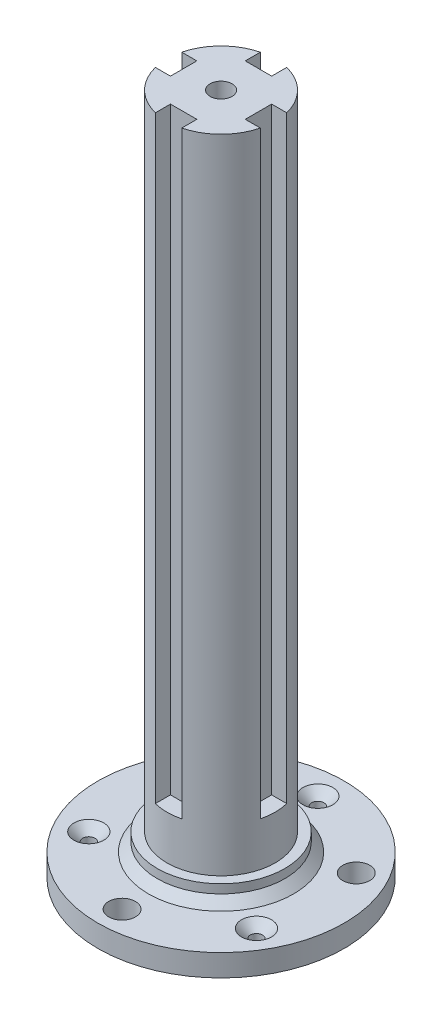
SolidWorks part; units mm, degrees
other "Marcação1"
sketch "Esboço14" plane through (-28, 0, 28) normal (-0.279, -0.8774, 0.3904) x (0.9389, -0.3346, -0.0809)
ref_plane "Plano frontal" through (0, 0, 0) normal (0, 0, 1) x (1, 0, 0)
ref_plane "Plano superior" through (0, 0, 0) normal (0, 1, 0) x (1, 0, 0)
ref_plane "Plano direito" through (0, 0, 0) normal (1, 0, 0) x (0, 0, -1)
sketch "Esboço1" plane through (0, 0, 0) normal (0, 1, 0) x (1, 0, 0)
  circle A0 centre (0, 0) radius 28
  dimension "D1" = 56
extrude "Ressalto-extrusão1" add sketch "Esboço1" along normal blind 5
sketch "Esboço5" plane through (0, 0, 0) normal (1, 0, 0) x (0, 0, -1)
  line L0 (0, 5) -> (-16.5, 5)
  line L1 (28, 5) -> (-28, 5) construction
  line L2 (-16.5, 5) -> (-14.5, 7)
  line L3 (-14.5, 7) -> (-14.5, 9)
  line L4 (-14.5, 9) -> (-12.3, 9)
  line L5 (-12.3, 9) -> (-12.3, 155)
  line L6 (-12.3, 155) -> (0, 155)
  line L7 (0, 155) -> (0, 5)
  dimension "D1" = 16.5
  dimension "D2" = 14.5
  dimension "D3" = 2
  dimension "D4" = 2
  dimension "D5" = 12.3
  dimension "D6" = 150
revolve "Revolução1" add sketch "Esboço5" angle 360 about L7
sketch "Esboço6" plane through (0, 0, 0) normal (0, -1, 0) x (1, 0, 0)
  circle A0 centre (0, 0) radius 10.75
  dimension "D1" = 21.5
extrude "Corte-extrusão1" cut sketch "Esboço6" against normal blind 5
sketch "Esboço7" plane through (0, 5, 0) normal (0, -1, 0) x (1, 0, 0)
  circle A0 centre (0, 0) radius 9
  dimension "D1" = 18
extrude "Corte-extrusão2" cut sketch "Esboço7" against normal blind 0.4
sketch "Esboço8" plane through (0, 0, 0) normal (0, -1, 0) x (1, 0, 0)
  line L0 (0, 0) -> (0, 22.5) construction
  circle A0 centre (0, 22.5) radius 3.05
  dimension "D2" = 6.1
  dimension "D1" = 22.5
extrude "Corte-extrusão3" cut sketch "Esboço8" against normal up to next
pattern_circular "PadrãoCircular1" count 3 over 360 about axis through (0, 0, 0) along (0, 1, 0) of "Corte-extrusão3"
sketch "Esboço9" plane through (0, 0, 0) normal (0, -1, 0) x (1, 0, 0)
  line L0 (0, 0) -> (0, 22.5) construction
  line L1 (0, 0) -> (-19.0526, 11) construction
  circle A0 centre (-19.0526, 11) radius 1.4
  dimension "D3" = 2.8
  dimension "D1" = 60
  dimension "D2" = 22
extrude "Corte-extrusão4" cut sketch "Esboço9" against normal up to next
pattern_circular "PadrãoCircular2" count 3 over 360 about axis through (0, 0, 0) along (0, 1, 0) of "Corte-extrusão4"
sketch "Esboço10" plane through (0, 0, 0) normal (0, -1, 0) x (1, 0, 0)
  line L0 (0, 0) -> (0, 22.5) construction
  line L1 (0, 0) -> (-17.6777, 17.6777) construction
  circle A0 centre (-17.6777, 17.6777) radius 1.25
  dimension "D3" = 2.5
  dimension "D1" = 45
  dimension "D2" = 25
ref_plane "Plano1" through (0, 3, 0) normal (0, -1, 0) x (-1, 0, 0)
sketch "Esboço12" plane through (0, 3, 0) normal (0, -1, 0) x (-1, 0, 0)
  circle A0 centre (17.6777, -17.6777) radius 0.75
  dimension "D1" = 1.5
loft "Loft de corte1" cut profiles "Esboço12", "Esboço10" connector at (-18.2603, 3, 17.2054) connector at (-18.9149, 0, 17.4992)
pattern_circular "PadrãoCircular3" count 3 over 360 about axis through (0, 0, 0) along (0, 1, 0) of "Loft de corte1"
chamfer "Chanfro1" distance 2 angle 45 1 edges at (-19.0526, 5, 12.4)
chamfer "Chanfro2" distance 2 angle 45 2 edges at (19.0526, 5, 12.4) (0, 5, -20.6)
sketch "Esboço17" plane through (0, 155, 0) normal (0, 1, 0) x (1, 0, 0)
  line L0 (0, 0) -> (0, 12.3) construction
  line L1 (-3, 8.5) -> (3, 8.5)
  line L2 (3, 8.5) -> (3, 11.9285)
  line L3 (-3, 8.5) -> (-3, 11.9285)
  circle A0 centre (0, 0) radius 12.3 construction
  arc A1 (3, 11.9285) -> (-3, 11.9285) centre (0, 0) ccw
  point P8 (0, 8.5)
  dimension "D2" = 3
  dimension "D3" = 8.5
extrude "Corte-extrusão5" cut sketch "Esboço17" against normal blind 136
pattern_circular "PadrãoCircular4" count 4 over 360 about axis through (0, 155, 0) along (0, 1, 0) of "Corte-extrusão5"
sketch "Esboço18" plane through (0, 155, 0) normal (0, 1, 0) x (1, 0, 0)
  circle A0 centre (0, 0) radius 2.5
  dimension "D1" = 5
extrude "Corte-extrusão6" cut sketch "Esboço18" against normal blind 10
